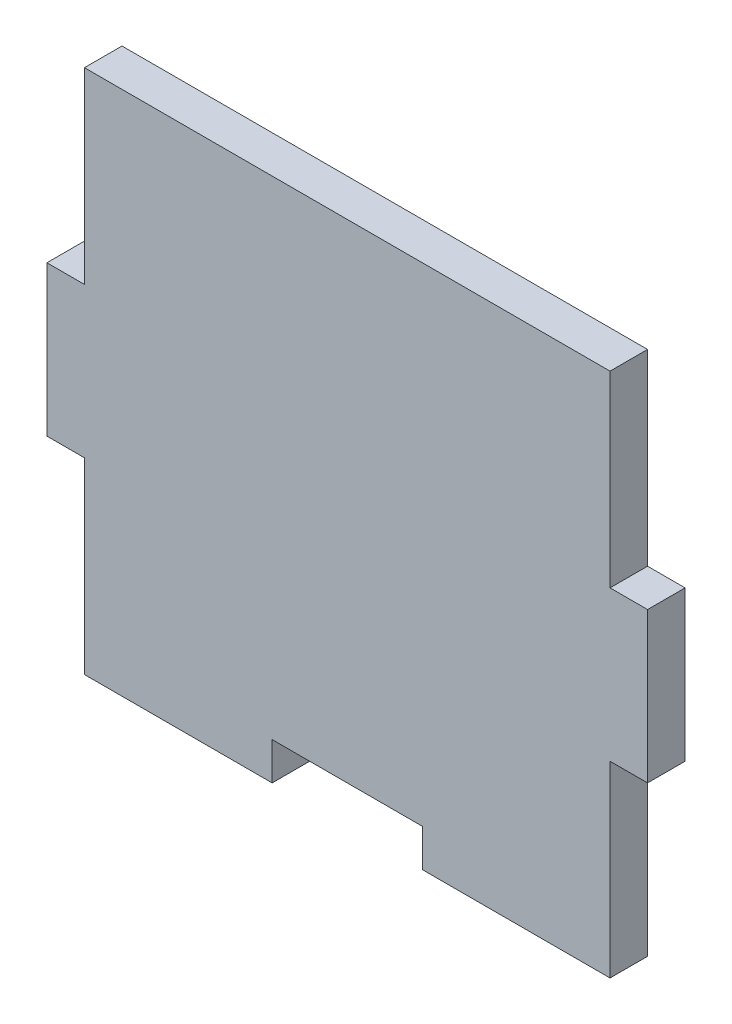
SolidWorks part; units mm, degrees
ref_plane "Front Plane" through (0, 0, 0) normal (0, 0, 1) x (1, 0, 0)
ref_plane "Top Plane" through (0, 0, 0) normal (0, 1, 0) x (1, 0, 0)
ref_plane "Right Plane" through (0, 0, 0) normal (1, 0, 0) x (0, 0, -1)
sketch "Sketch1" plane through (0, 0, 0) normal (0, 0, 1) x (1, 0, 0)
  line L0 (-64.6057, 59.3342) -> (-64.6057, -48.6158) construction
  line L1 (-109.0557, 59.3342) -> (-20.1557, 59.3342)
  line L2 (-109.0557, 59.3342) -> (-109.0557, -29.5658)
  line L3 (-109.0557, -29.5658) -> (-77.3057, -29.5658)
  line L4 (-20.1557, 59.3342) -> (-20.1557, -29.5658)
  line L5 (-109.0557, 14.8842) -> (-20.1557, 14.8842) construction
  line L6 (-13.8057, 2.1842) -> (-20.1557, 2.1842)
  line L7 (-115.4057, 27.5842) -> (-109.0557, 27.5842)
  line L8 (-115.4057, 27.5842) -> (-115.4057, 2.1842)
  line L9 (-115.4057, 2.1842) -> (-109.0557, 2.1842)
  line L10 (-51.9057, -29.5658) -> (-44.9709, -29.5658) construction
  line L11 (-51.9057, -29.5658) -> (-44.9709, -29.5658)
  line L13 (-77.3057, -29.5658) -> (-51.9057, -29.5658)
  line L14 (-77.3057, -29.5658) -> (-77.3057, -23.2158)
  line L15 (-13.8057, 27.5842) -> (-13.8057, 2.1842)
  line L16 (-13.8057, 27.5842) -> (-20.1557, 27.5842)
  line L17 (-77.3057, -23.2158) -> (-51.9057, -23.2158)
  line L18 (-51.9057, -29.5658) -> (-51.9057, -23.2158)
  line L27 (-20.1557, -29.5658) -> (-51.9057, -29.5658)
  dimension "D1" = 88.9
  dimension "D2" = 88.9
  dimension "D3" = 6.35
  dimension "D4" = 25.4
  dimension "D5" = 31.75
  dimension "D6" = 25.4
  dimension "D7" = 6.35
extrude "Boss-Extrude1" add sketch "Sketch1" along normal blind 6.35 contours L27 L4 L1 L2 L3 L14 L17 | L8 L9 L2 L7 | L15 L16 L4 L6 region at (-64.6057, 15.7441, 0) region at (-112.2307, 14.8842, 0) region at (-16.9807, 14.8842, 0)
equation "\"width\"= 3.5in"
equation "\"Height\"= 18in"
equation "\"thick\"= 0.25"
equation "\"D1@Sketch1\"=\"width\""
equation "\"D3@Sketch1\"=\"thick\""
equation "\"D1@Boss-Extrude1\"=\"thick\""
equation "\"D2@Sketch1\"=\"width\""
equation "\"D7@Sketch1\"=\"thick\""
